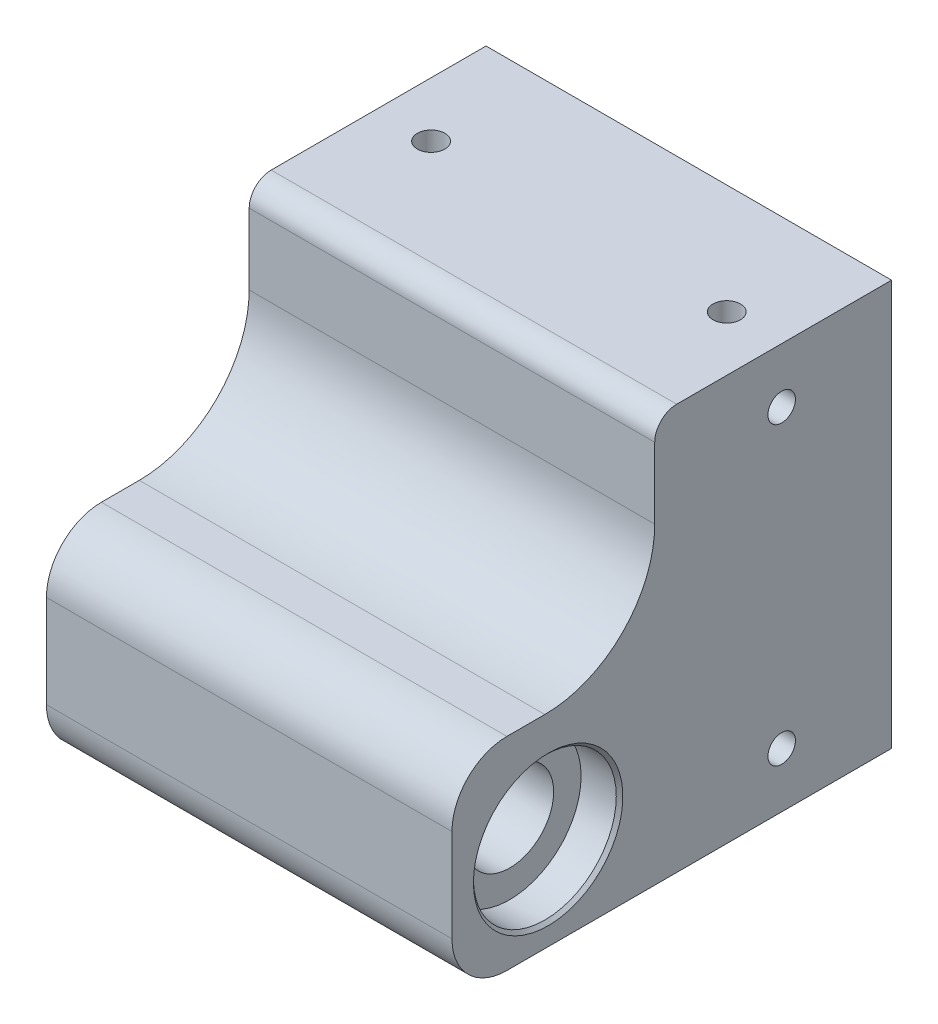
SolidWorks part; units mm, degrees
material "6061 合金"
ref_plane "前视基准面" through (0, 0, 0) normal (0, 0, 1) x (1, 0, 0)
ref_plane "上视基准面" through (0, 0, 0) normal (0, 1, 0) x (1, 0, 0)
ref_plane "右视基准面" through (0, 0, 0) normal (1, 0, 0) x (0, 0, -1)
sketch "草图1" plane through (0, 0, 0) normal (0, 0, 1) x (1, 0, 0)
  line L1 (-18.45, -18.45) -> (18.45, -18.45)
  line L2 (-18.45, -18.45) -> (-18.45, 18.45)
  line L3 (-18.45, 18.45) -> (18.45, 18.45)
  line L4 (18.45, -18.45) -> (18.45, 18.45)
  line L5 (0, 18.45) -> (0, -18.45) construction
  line L6 (-18.45, 0) -> (18.45, 0) construction
  point P0 (0, 0)
  dimension "D1" = 36.9
  dimension "D2" = 36.9
extrude "凸台-拉伸1" add sketch "草图1" along normal mid plane 40
sketch "草图2" plane through (18.45, 0, 0) normal (1, 0, 0) x (0, 0, -1)
  line L1 (-1.5, 18.5) -> (-20, 0)
  line L2 (0, 0) -> (-20, 0) construction
  line L3 (-20, 0) -> (-20, 18.5)
  line L4 (-20, 18.5) -> (-1.5, 18.5)
  line L5 (-11.25, 0) -> (-11.25, -10) construction
  line L6 (-20, -18.45) -> (-20, 18.45) construction
  circle A1 centre (-11.25, -10) radius 4
  dimension "D5" = 8
  dimension "D1" = 8.75
  dimension "D2" = 18.5
  dimension "D3" = 18.5
  dimension "D4" = 10
extrude "切除-拉伸1" cut sketch "草图2" against normal blind 36.9
sketch "草图3" plane through (18.45, 0, 0) normal (1, 0, 0) x (0, 0, -1)
  circle A0 centre (-11.25, -10) radius 6.5
  dimension "D1" = 13
extrude "切除-拉伸2" cut sketch "草图3" against normal blind 3.5
mirror "镜向1" about plane through (0, 0, 0) normal (1, 0, 0) of "切除-拉伸2"
sketch "草图4" plane through (18.45, 0, 0) normal (1, 0, 0) x (0, 0, -1)
  line L0 (-20, 0) -> (-1.55, 0)
  line L1 (-1.55, 0) -> (-1.55, 18.45)
  line L2 (-20, 0) -> (-1.55, 18.45) construction
  line L3 (-20, 0) -> (-1.55, 18.45)
extrude "切除-拉伸3" cut sketch "草图4" against normal blind 51
fillet "圆角1" radius 10 1 edges at (0, 0, 1.55)
fillet "圆角2" radius 5 2 edges at (0, -18.45, 20) (0, 0, 20)
sketch "草图5" plane through (0, 0, -20) normal (0, 0, -1) x (-1, 0, 0)
  line L0 (-18.45, 18.45) -> (18.45, 18.45) construction
  line L1 (-8.45, -15.45) -> (8.45, -15.45)
  line L2 (-8.45, -15.45) -> (-8.45, 15.45)
  line L3 (-8.45, 15.45) -> (8.45, 15.45)
  line L4 (8.45, -15.45) -> (8.45, 15.45)
  line L5 (0, 15.45) -> (0, -15.45) construction
  line L6 (-8.45, 0) -> (8.45, 0) construction
  line L7 (-15.45, -8.45) -> (15.45, -8.45)
  line L8 (-15.45, -8.45) -> (-15.45, 8.45)
  line L9 (-15.45, 8.45) -> (15.45, 8.45)
  line L10 (15.45, -8.45) -> (15.45, 8.45)
  line L11 (0, 8.45) -> (0, -8.45) construction
  line L12 (-15.45, 0) -> (15.45, 0) construction
  line L13 (18.45, 18.45) -> (18.45, -18.45) construction
  line L14 (-18.45, -18.45) -> (-18.45, 18.45) construction
  point P0 (0, 0)
  point P4 (0, 0)
  dimension "D1" = 3
  dimension "D2" = 3
  dimension "D3" = 10
  dimension "D4" = 10
extrude "切除-拉伸4" cut sketch "草图5" against normal offset from surface (16.55 mm away) 5 contours L9 L2 L7 L4 | L9 L8 L7 L2 | L2 L9 L4 L3 | L7 L10 L9 L4 | L7 L2 L1 L4 region at (0, -11.95, -20) region at (11.95, 0, -20) region at (0, 0, -20) region at (-11.95, 0, -20) region at (0, 11.95, -20) up to face at (0, 14.225, 1.55)
sketch "草图6" plane through (0, 18.45, 0) normal (0, 1, 0) x (1, 0, 0)
  line L0 (-13.45, 10) -> (13.45, 10) construction
  line L1 (18.45, -1.55) -> (18.45, 20) construction
  line L2 (0, 10) -> (0, 0) construction
  line L3 (18.45, 20) -> (-18.45, 20) construction
  dimension "D1" = 5
  dimension "D2" = 10
hole_wizard "M3 螺纹孔1" positions "草图7" profile "草图8" tap size "M3" standard "GB" end condition up to next
sketch "草图7" plane through (0, 18.45, 0) normal (0, 1, 0) x (1, 0, 0)
  point P0 (-13.45, 10)
  point P3 (13.45, 10)
sketch "草图8" plane through (-13.45, 18.45, -10) normal (1, 0, 0) x (0, 0, 1)
  line L0 (0, 0) -> (0, 10)
  line L1 (0, 10) -> (1.25, 10)
  line L2 (1.25, 10) -> (1.25, 0)
  line L5 (1.25, 0) -> (0, 0)
  line L11 (0, -6.35) -> (0, 107.95) construction
  dimension "通孔螺纹孔钻头直径" = 2.5
  dimension "通孔螺纹孔钻头深度" = 10
cosmetic thread "孔螺蚊线1" parameters "D2"=3
cosmetic thread "孔螺蚊线2" parameters "D2"=3
sketch "草图9" plane through (18.45, 0, 0) normal (1, 0, 0) x (0, 0, -1)
  line L0 (20, -13.45) -> (10, -13.45) construction
  line L1 (20, -18.45) -> (20, 18.45) construction
  line L2 (-15, -18.45) -> (20, -18.45) construction
  dimension "D1" = 5
  dimension "D2" = 10
hole_wizard "M3 螺纹孔2" positions "草图10" profile "草图11" tap size "M3" standard "GB" end condition through all
sketch "草图10" plane through (18.45, 0, 0) normal (1, 0, 0) x (0, 0, -1)
  point P0 (10, -13.45)
sketch "草图11" plane through (18.45, -13.45, -10) normal (0, 1, 0) x (0, 0, -1)
  line L0 (0, 0) -> (0, 36.9)
  line L1 (0, 36.9) -> (1.25, 36.9)
  line L2 (1.25, 36.9) -> (1.25, 0)
  line L5 (1.25, 0) -> (0, 0)
  line L11 (0, -6.35) -> (0, 107.95) construction
  dimension "通孔螺纹孔钻头直径" = 2.5
  dimension "通孔螺纹孔钻头深度" = 36.9
cosmetic thread "孔螺蚊线3" parameters "D2"=3
mirror "镜向2" about plane through (0, 0, 0) normal (1, 0, 0) of "M3 螺纹孔2"
cosmetic thread "孔螺蚊线4" parameters "D2"=3
sketch "草图12" plane through (0, -18.45, 0) normal (0, -1, 0) x (1, 0, 0)
  line L0 (-10, -5) -> (10, -5) construction
  line L1 (-18.45, -20) -> (18.45, -20) construction
  line L2 (0, 0) -> (0, -5) construction
  point P3 (0, -5)
  dimension "D1" = 15
  dimension "D2" = 20
hole_wizard "M3 螺纹孔3" positions "草图13" profile "草图14" tap size "M3" standard "GB" end condition up to next
sketch "草图13" plane through (0, -18.45, 0) normal (0, -1, 0) x (-1, 0, 0)
  point P0 (10, 5)
  point P3 (-10, 5)
cosmetic thread "孔螺蚊线5" parameters "D2"=3
cosmetic thread "孔螺蚊线6" parameters "D2"=3
sketch "草图14" plane through (-10, -18.45, -5) normal (1, 0, 0) x (0, 0, -1)
  line L0 (0, 0) -> (0, 10)
  line L1 (0, 10) -> (1.25, 10)
  line L2 (1.25, 10) -> (1.25, 0)
  line L5 (1.25, 0) -> (0, 0)
  line L11 (0, -6.35) -> (0, 107.95) construction
  dimension "通孔螺纹孔钻头直径" = 2.5
  dimension "通孔螺纹孔钻头深度" = 10
fillet "圆角3" radius 2 12 edges at (-15.45, -8.45, -11.725) (-8.45, -8.45, -11.725) (-8.45, -15.45, -11.725) (8.45, -15.45, -11.725) (8.45, -8.45, -11.725) (15.45, -8.45, -11.725) (15.45, 8.45, -11.725) (-8.45, 15.45, -11.725) (-8.45, 8.45, -11.725) (-15.45, 8.45, -11.725) (8.45, 15.45, -11.725) (8.45, 8.45, -11.725)
fillet "圆角7" radius 2 1 edges at (0, 18.45, 1.55)
mirror "镜向3" about plane through (0, 0, 0) normal (0, 1, 0) of "M3 螺纹孔2"
cosmetic thread "孔螺蚊线7" parameters "D2"=3
chamfer "倒角1" distance 0.3 angle 45 2 edges at (18.45, -10, 4.75) (-18.45, -10, 4.75)
